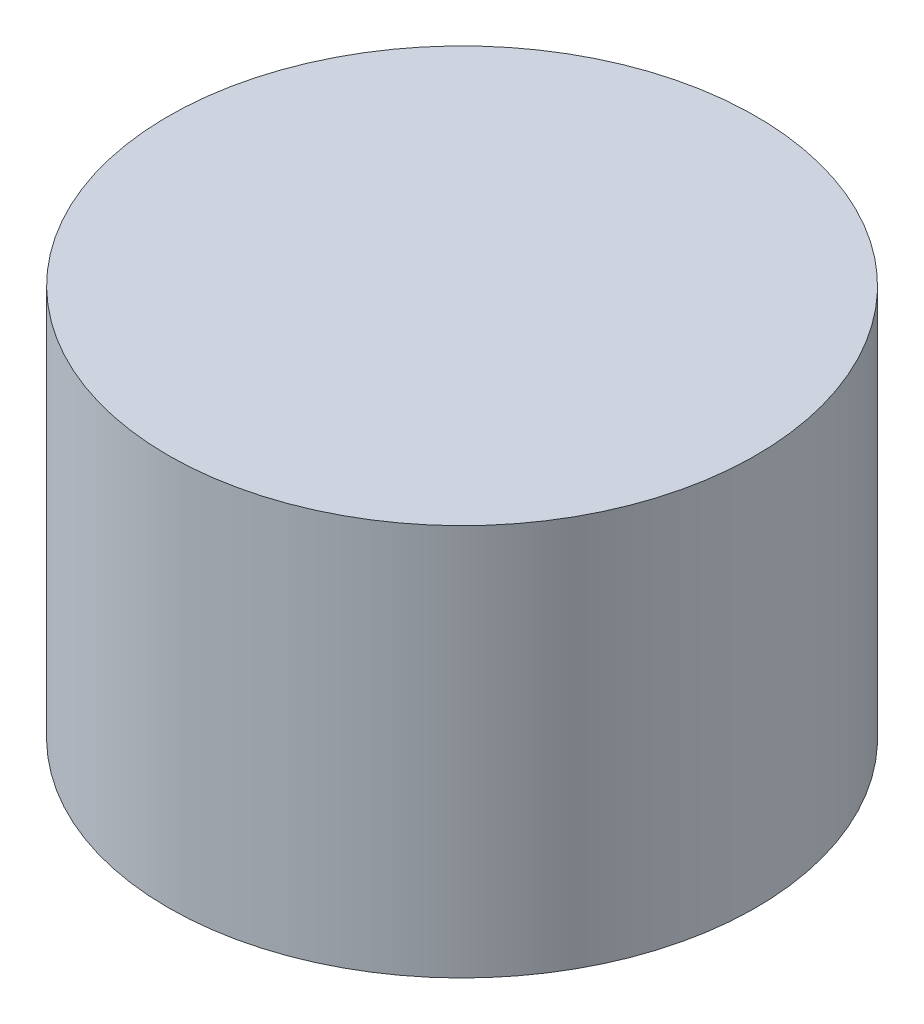
SolidWorks part; units mm, degrees
ref_plane "Front" through (0, 0, 0) normal (0, 0, 1) x (1, 0, 0)
ref_plane "Top" through (0, 0, 0) normal (0, 1, 0) x (1, 0, 0)
ref_plane "Right" through (0, 0, 0) normal (1, 0, 0) x (0, 0, -1)
sketch "Sketch1" plane through (0, 0, 0) normal (0, 1, 0) x (1, 0, 0)
  circle A0 centre (0, 0) radius 4.7625
  dimension "D1" = 9.525
extrude "Boss-Extrude1" add sketch "Sketch1" along normal blind 6.35
